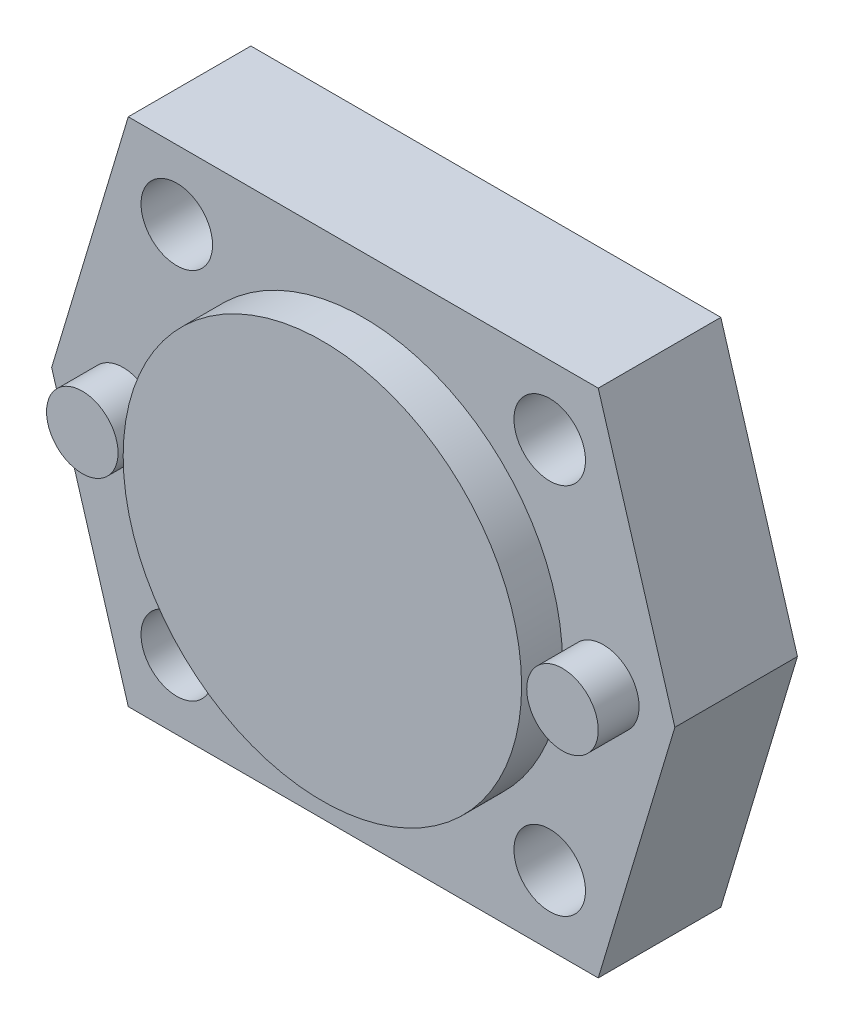
SolidWorks part; units mm, degrees
ref_plane "Front Plane" through (0, 0, 0) normal (0, 0, 1) x (1, 0, 0)
ref_plane "Top Plane" through (0, 0, 0) normal (0, 1, 0) x (1, 0, 0)
ref_plane "Right Plane" through (0, 0, 0) normal (1, 0, 0) x (0, 0, -1)
sketch "Sketch1" plane through (0, 0, 0) normal (0, 0, 1) x (1, 0, 0)
  line L0 (-23, 25) -> (23, 25)
  line L1 (23, 25) -> (30.5, 0)
  line L2 (30.5, 0) -> (23, -25)
  line L3 (23, -25) -> (-23, -25)
  line L4 (-23, -25) -> (-30.5, 0)
  line L5 (-30.5, 0) -> (-23, 25)
  line L6 (-30.5, 0) -> (30.5, 0) construction
  line L7 (0, 25) -> (0, -25) construction
  line L8 (-23, 25) -> (-23, -25) construction
  line L9 (23, -25) -> (23, 25) construction
  point P8 (0, 0)
  point P10 (0, 0)
  dimension "D1" = 50
  dimension "D2" = 61
  dimension "D3" = 46
extrude "Boss-Extrude1" add sketch "Sketch1" along normal blind 12
sketch "Sketch2" plane through (0, 0, 12) normal (0, 0, 1) x (1, 0, 0)
  line L0 (-30.5, 0) -> (30.5, 0) construction
  circle A0 centre (0, 0) radius 19.5
  circle A1 centre (23.5, 0) radius 3.5
  circle A2 centre (-23.5, 0) radius 3.5
  dimension "D1" = 39
  dimension "D2" = 7
  dimension "D3" = 23.5
  dimension "D4" = 23.5
extrude "Boss-Extrude2" add sketch "Sketch2" along normal blind 4
fillet "Fillet1" [suppressed] radius 2
sketch "Sketch3" plane through (0, 0, 12) normal (0, 0, 1) x (1, 0, 0)
  line L1 (-18.25, -18.25) -> (18.25, -18.25) construction
  line L2 (-18.25, -18.25) -> (-18.25, 18.25) construction
  line L3 (-18.25, 18.25) -> (18.25, 18.25) construction
  line L4 (18.25, -18.25) -> (18.25, 18.25) construction
  line L5 (-18.25, -18.25) -> (18.25, 18.25) construction
  line L6 (-18.25, 18.25) -> (18.25, -18.25) construction
  circle A0 centre (18.25, 18.25) radius 3.5
  circle A1 centre (18.25, -18.25) radius 3.5
  circle A2 centre (-18.25, -18.25) radius 3.5
  circle A3 centre (-18.25, 18.25) radius 3.5
  point P0 (0, 0)
  dimension "D3" = 7
  dimension "D1" = 36.5
  dimension "D2" = 36.5
extrude "Cut-Extrude1" cut sketch "Sketch3" against normal blind 12
